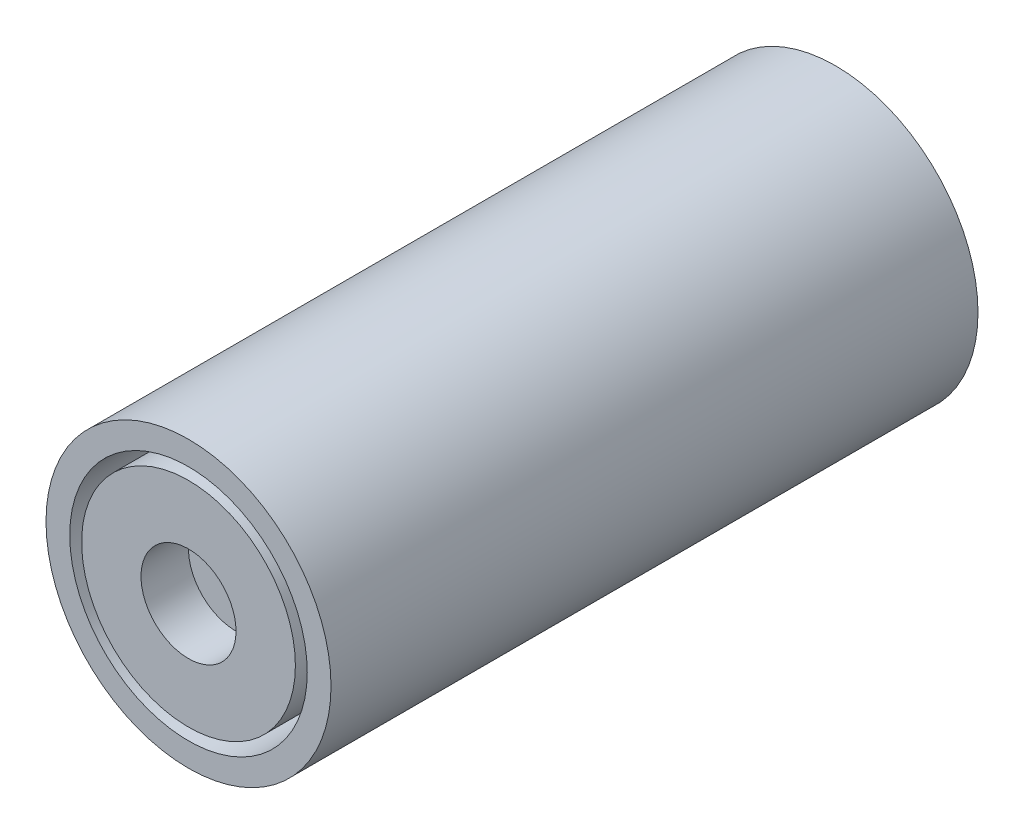
SolidWorks part; units mm, degrees
material "Brass"
ref_plane "Front Plane" through (0, 0, 0) normal (0, 0, 1) x (1, 0, 0)
ref_plane "Top Plane" through (0, 0, 0) normal (0, 1, 0) x (1, 0, 0)
ref_plane "Right Plane" through (0, 0, 0) normal (1, 0, 0) x (0, 0, -1)
sketch "Sketch1" plane through (0, 0, 0) normal (0, 0, 1) x (1, 0, 0)
  circle A0 centre (0, 0) radius 3.81
  circle A1 centre (0, 0) radius 1.27
  circle A2 centre (0, 0) radius 2.8575
  circle A3 centre (0, 0) radius 3.175
  dimension "D1" = 7.62
  dimension "D2" = 2.54
  dimension "D3" = 5.715
  dimension "D4" = 6.35
extrude "Boss-Extrude1" add sketch "Sketch1" against normal blind 17.2974 contours A0
extrude "Cut-Extrude1" cut sketch "Sketch1<6>" against normal blind 2.54 contours A3 | A2
sketch "Sketch1<6>" plane through (0, 0, 0) normal (0, 0, 1) x (1, 0, 0) same geometry as "Sketch1"
extrude "Cut-Extrude2" cut sketch "Sketch1<7>" against normal blind 1.27 contours A1
sketch "Sketch1<7>" plane through (0, 0, 0) normal (0, 0, 1) x (1, 0, 0) same geometry as "Sketch1"
